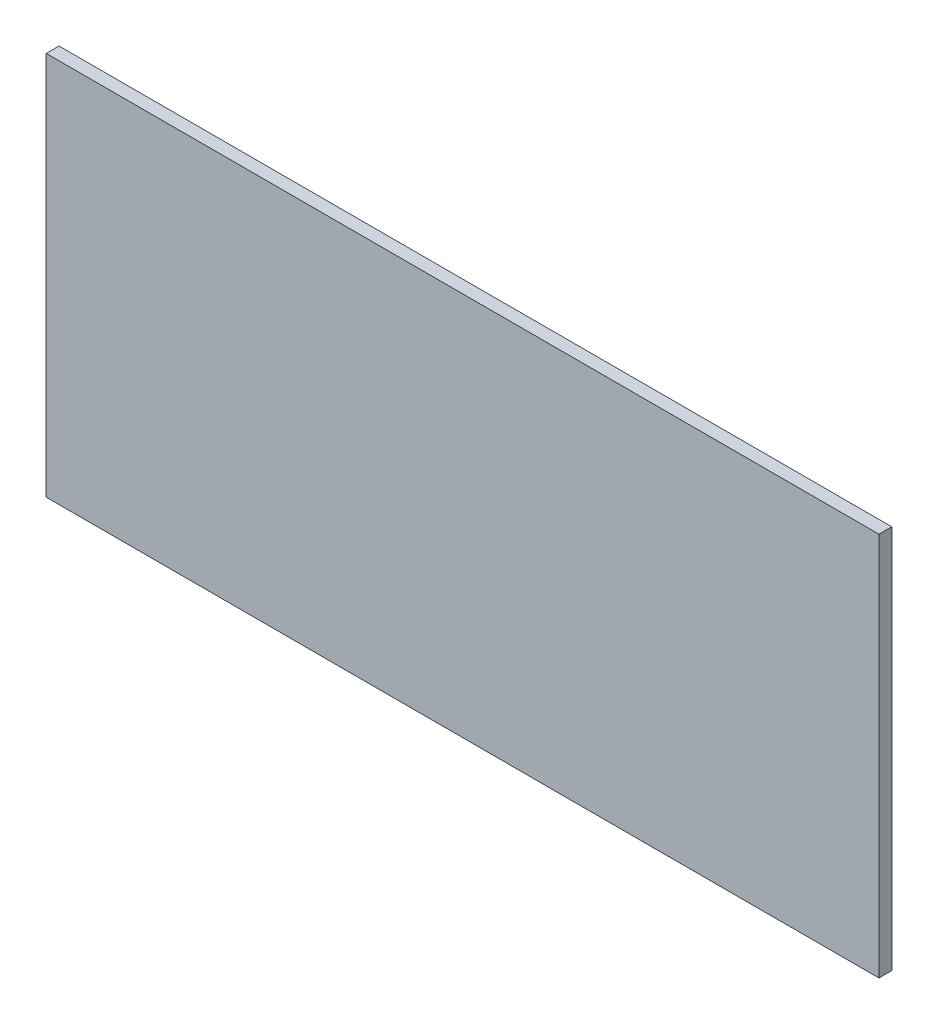
SolidWorks part; units mm, degrees
ref_plane "Front Plane" through (0, 0, 0) normal (0, 0, 1) x (1, 0, 0)
ref_plane "Top Plane" through (0, 0, 0) normal (0, 1, 0) x (1, 0, 0)
ref_plane "Right Plane" through (0, 0, 0) normal (1, 0, 0) x (0, 0, -1)
sketch "Sketch1" plane through (0, 0, 0) normal (0, 0, 1) x (1, 0, 0)
  line L0 (125.9407, 9.445) -> (125.9407, -9.555) construction
  line L1 (100.9407, 9.445) -> (150.9407, 9.445) construction
  line L2 (150.9407, -9.555) -> (100.9407, -9.555) construction
  line L3 (93.4407, 14.945) -> (93.4407, -15.055) construction
  line L5 (158.4407, -15.055) -> (158.4407, 14.945) construction
  line L6 (158.4407, 14.945) -> (93.4407, 14.945) construction
  line L7 (93.4407, 14.945) -> (93.4407, -15.055) construction
  line L8 (158.4407, -15.055) -> (93.4407, 14.945) construction
  line L9 (158.4407, 14.945) -> (93.4407, -15.055) construction
  line L12 (158.4407, 14.945) -> (93.4407, 14.945) construction
  line L13 (93.4407, -15.055) -> (93.4407, 14.945)
  line L14 (93.4407, 14.945) -> (158.4407, 14.945)
  line L15 (158.4407, 14.945) -> (158.4407, -15.055)
  line L16 (158.4407, -15.055) -> (93.4407, -15.055)
  point P6 (125.9407, -0.055)
  dimension "D1" = 65
  dimension "D2" = 30
extrude "Boss-Extrude1" add sketch "Sketch1" against normal blind 1
sketch "Sketch2" plane through (0, 0, -1) normal (0, 0, -1) x (-1, 0, 0)
  line L0 (-150.9407, 6.945) -> (-100.9407, 6.945) construction
  line L1 (-150.9407, -9.555) -> (-150.9407, 9.445) construction
  line L2 (-100.9407, -9.555) -> (-100.9407, 9.445) construction
  line L3 (-150.9407, -7.055) -> (-100.9407, -7.055) construction
  line L4 (-103.4407, 9.445) -> (-103.4407, -9.555) construction
  line L5 (-100.9407, 9.445) -> (-150.9407, 9.445) construction
  line L6 (-150.9407, -9.555) -> (-100.9407, -9.555) construction
  line L7 (-148.4407, 9.445) -> (-148.4407, -9.555) construction
  line L8 (-148.4407, 9.445) -> (-103.4407, 9.445)
  line L9 (-100.9407, 6.945) -> (-100.9407, -7.055)
  line L10 (-103.4407, -9.555) -> (-148.4407, -9.555)
  line L12 (-150.9407, -7.055) -> (-150.9407, 6.945)
  arc A0 (-150.9407, 6.945) -> (-148.4407, 9.445) centre (-148.4407, 6.945) cw
  arc A1 (-103.4407, 9.445) -> (-100.9407, 6.945) centre (-103.4407, 6.945) cw
  arc A2 (-103.4407, -9.555) -> (-100.9407, -7.055) centre (-103.4407, -7.055) ccw
  arc A3 (-148.4407, -9.555) -> (-150.9407, -7.055) centre (-148.4407, -7.055) cw
  dimension "D1" = 2.5
extrude "Boss-Extrude2" add sketch "Sketch2" along normal blind 2 separate body
